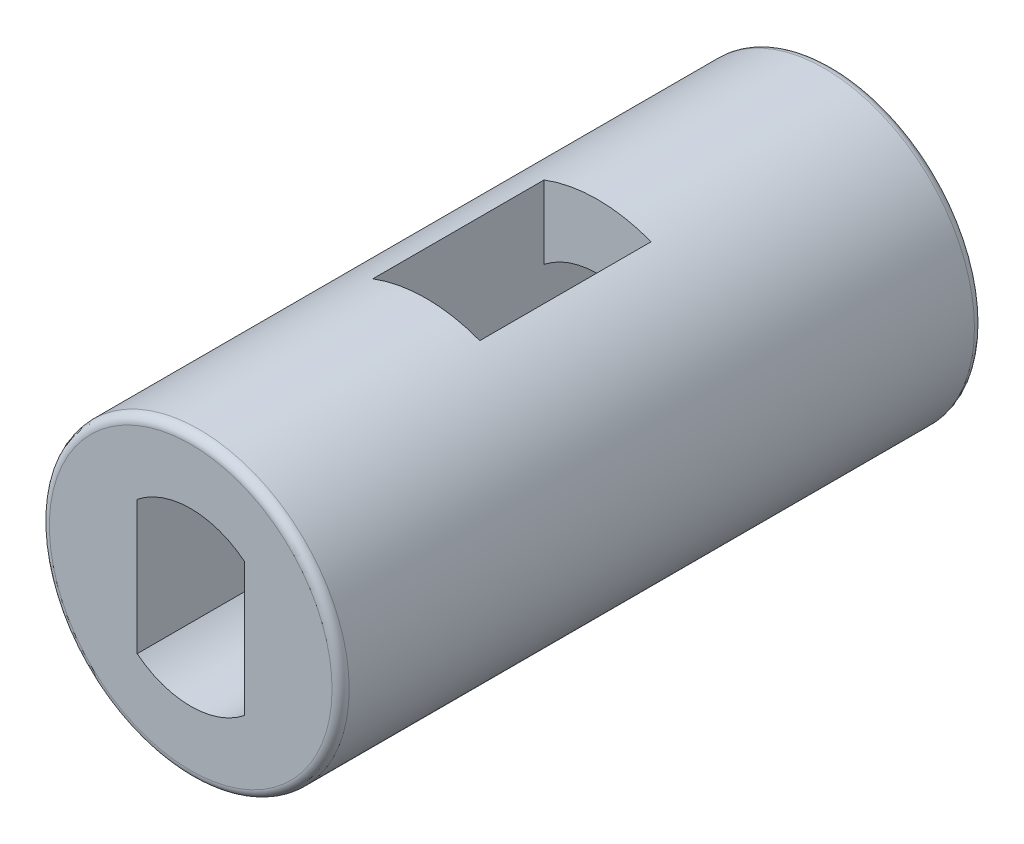
SolidWorks part; units mm, degrees
ref_plane "前视基准面" through (0, 0, 0) normal (0, 0, 1) x (1, 0, 0)
ref_plane "上视基准面" through (0, 0, 0) normal (0, 1, 0) x (1, 0, 0)
ref_plane "右视基准面" through (0, 0, 0) normal (1, 0, 0) x (0, 0, -1)
sketch "草图1" plane through (0, 0, 0) normal (0, 0, 1) x (1, 0, 0)
  line L2 (-1.25, 1.5612) -> (-1.25, -1.5612)
  line L4 (1.25, 1.5612) -> (1.25, -1.5612)
  arc A0 (1.25, 1.5612) -> (-1.25, 1.5612) centre (0, 0) ccw
  circle A1 centre (0, 0) radius 3.5
  arc A2 (-1.25, -1.5612) -> (1.25, -1.5612) centre (0, 0) ccw
extrude "凸台-拉伸1" add sketch "草图1" against normal blind 7.5 and the other way blind 7.5
sketch "草图2" plane through (0, 0, 0) normal (0, 1, 0) x (1, 0, 0)
  line L1 (-1.25, 2) -> (1.25, 2)
  line L2 (-1.25, 2) -> (-1.25, -2)
  line L3 (-1.25, -2) -> (1.25, -2)
  line L4 (1.25, 2) -> (1.25, -2)
extrude "切除-拉伸1" cut sketch "草图2" against normal up to next and the other way up to next
fillet "圆角1" radius 0.2 2 edges at (3.5, 0, -7.5) (3.5, 0, 7.5)
